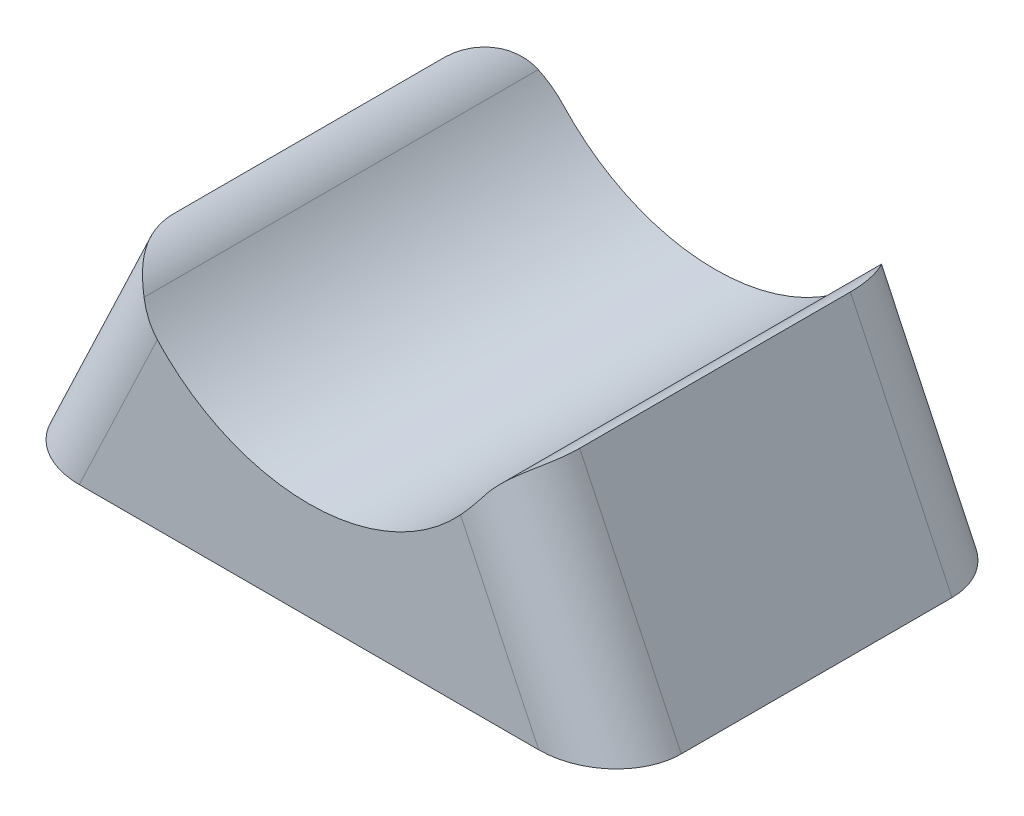
SolidWorks part; units mm, degrees
ref_plane "Front Plane" through (0, 0, 0) normal (0, 0, 1) x (1, 0, 0)
ref_plane "Top Plane" through (0, 0, 0) normal (0, 1, 0) x (1, 0, 0)
ref_plane "Right Plane" through (0, 0, 0) normal (1, 0, 0) x (0, 0, -1)
sketch "Sketch1" plane through (0, 0, 0) normal (0, 1, 0) x (1, 0, 0)
  line L1 (-6, 6) -> (6, 6)
  line L2 (-6, 6) -> (-6, -6)
  line L3 (-6, -6) -> (6, -6)
  line L4 (6, 6) -> (6, -6)
  line L5 (-6, 6) -> (6, -6) construction
  line L6 (-6, -6) -> (6, 6) construction
  point P0 (0, 0)
  dimension "D1" = 12
extrude "Boss-Extrude1" add sketch "Sketch1" along normal blind 17
sketch "Sketch3" plane through (0, 0, 0) normal (0, 0, 1) x (1, 0, 0)
  line L0 (-6, 0) -> (-9, 0)
  line L1 (-9, 0) -> (-6, 6.3246)
  line L2 (-6, 17) -> (-6, 0) construction
  line L3 (-6, 6.3246) -> (-6, 0)
  line L4 (6, 0) -> (9, 0)
  line L5 (9, 0) -> (6, 6.3246)
  line L6 (6, 17) -> (6, 0) construction
  line L7 (6, 6.3246) -> (6, 0)
  dimension "D1" = 3
  dimension "D2" = 7
  dimension "D3" = 3
  dimension "D4" = 7
extrude "Boss-Extrude2" add sketch "Sketch3" along normal blind 6 and the other way blind 6
sketch "Sketch4" plane through (0, 0, 6) normal (0, 0, 1) x (1, 0, 0)
  line L0 (0, 17) -> (0, 1) construction
  line L2 (-6, 17) -> (6, 17) construction
  circle A1 centre (0, 9) radius 6.1
  dimension "D1" = 16
  dimension "D2" = 12.2
extrude "Cut-Extrude1" cut sketch "Sketch4" against normal blind 16
fillet "Fillet1" radius 2 1 edges at (7.5, 3.1623, 6)
fillet "Fillet2" radius 2 1 edges at (6, 4.7789, 6)
fillet "Fillet3" radius 2 1 edges at (7.5, 3.1623, -6)
fillet "Fillet4" radius 2 1 edges at (6, 4.7789, -6)
fillet "Fillet5" radius 2 2 edges at (-7.5, 3.1623, -6) (-7.5, 3.1623, 6)
fillet "Fillet6" radius 2 2 edges at (-6, 4.7789, 6) (-6, 4.7789, -6)
fillet "Fillet9" radius 2 2 edges at (6, 7.9, 0) (-6, 7.9, 0)
